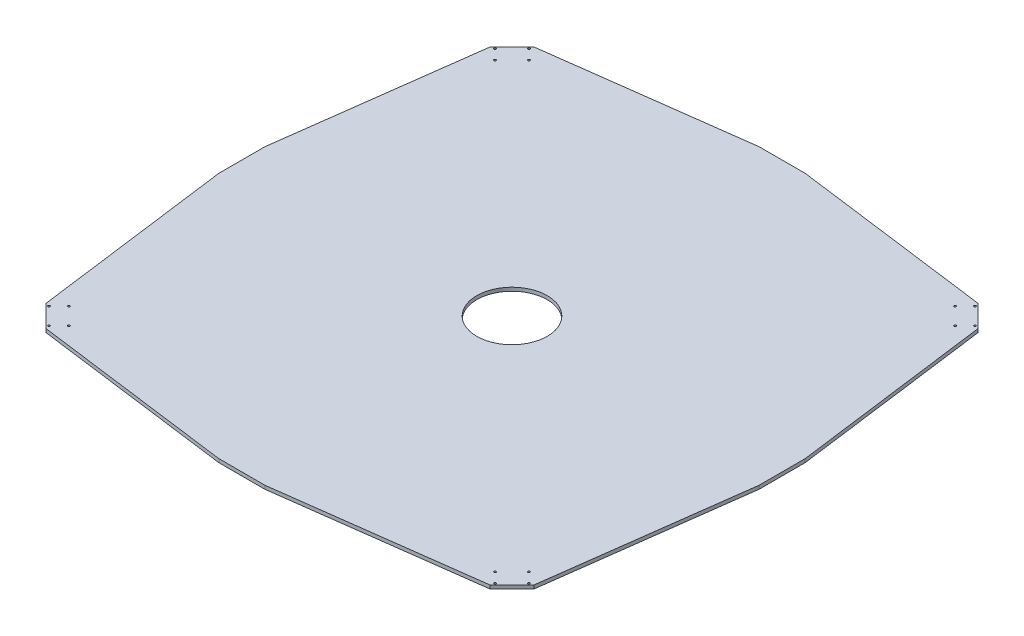
SolidWorks part; units mm, degrees
ref_plane "前视基准面" through (0, 0, 0) normal (0, 0, 1) x (1, 0, 0)
ref_plane "上视基准面" through (0, 0, 0) normal (0, 1, 0) x (1, 0, 0)
ref_plane "右视基准面" through (0, 0, 0) normal (1, 0, 0) x (0, 0, -1)
other "Configuration Table"
sketch "草图1" plane through (0, 0, 0) normal (0, 1, 0) x (1, 0, 0)
  line L0 (-314.9222, 345.9222) -> (-345.9222, 314.9222)
  line L5 (325, -325) -> (-325, 325) construction
  line L6 (325, 325) -> (-325, -325) construction
  line L7 (0, 325) -> (0, -325) construction
  line L8 (-325, 0) -> (325, 0) construction
  line L9 (314.9222, 345.9222) -> (32.7201, 383.0748)
  line L10 (314.9222, 345.9222) -> (345.9222, 314.9222)
  line L12 (-314.9222, 345.9222) -> (-32.7201, 383.0748)
  line L13 (0, 325) -> (0, 399.6983)
  line L14 (-32.7201, 383.0748) -> (32.7201, 383.0748)
  line L15 (314.9222, -345.9222) -> (32.7201, -383.0748)
  line L16 (-32.7201, -383.0748) -> (32.7201, -383.0748)
  line L17 (-314.9222, -345.9222) -> (-32.7201, -383.0748)
  line L18 (-314.9222, -345.9222) -> (-345.9222, -314.9222)
  line L19 (-345.9222, 314.9222) -> (-383.0748, 32.7201)
  line L20 (-383.0748, -32.7201) -> (-383.0748, 32.7201)
  line L21 (-345.9222, -314.9222) -> (-383.0748, -32.7201)
  line L22 (-345.9222, -314.9222) -> (-314.9222, -345.9222)
  line L23 (345.9222, -314.9222) -> (314.9222, -345.9222)
  line L24 (345.9222, -314.9222) -> (383.0748, -32.7201)
  line L25 (383.0748, 32.7201) -> (383.0748, -32.7201)
  line L26 (345.9222, 314.9222) -> (383.0748, 32.7201)
  line L27 (-337.8712, -313.8296) -> (-342.443, -318.4014)
  line L28 (-314.9222, -345.9222) -> (-293.6978, -324.6978)
  line L29 (-326.1795, -302.1379) -> (-298.6587, -329.6587)
  line L30 (-345.9222, -314.9222) -> (-325, -294)
  line L31 (-326.1795, -302.1379) -> (-329.6587, -298.6587)
  line L32 (-313.4871, -289.4455) -> (-337.8712, -313.8296)
  line L33 (-289.4455, -313.4871) -> (-313.8296, -337.8712)
  line L34 (-313.8296, -337.8712) -> (-318.4014, -342.443)
  circle A1 centre (-326.1795, -302.1379) radius 1.5
  circle A2 centre (-302.1379, -326.1795) radius 1.5
  circle A3 centre (-340.3217, -316.28) radius 1.5
  circle A4 centre (-316.28, -340.3217) radius 1.5
  circle A5 centre (0, 0) radius 50
  point P0 (0, 0)
  point P13 (0, 383.0748)
  point P24 (-330.4222, -330.4222)
  point P44 (-326.1795, -302.1379)
  point P45 (-302.1379, -326.1795)
  dimension "D6" = 3
  dimension "D7" = 20
  dimension "D8" = 100
  dimension "D1" = 650
  dimension "D2" = 650
  dimension "D3" = 31
  dimension "D4" = 142.5
  dimension "D5" = 17
extrude "凸台-拉伸2" add sketch "草图1" along normal blind 5 contours L26 L10 L9 L14 L12 L0 L19 L20 L21 L18 L17 L16 L15 L23 L24 L25 | A2 L29 A1 L32 L27 L22 L34 L33 | A1 L31 L30 L22 L27 L32 | A2 L33 L34 L18 L28 L29 region at (-172.4069, 0, -353.7562) region at (-336.0431, 0, 308.3956) region at (-322.2706, 0, 322.2706) region at (-308.3956, 0, 336.0431)
sketch "草图2" plane through (0, 5, 0) normal (0, 1, 0) x (1, 0, 0)
  line L0 (0, 0) -> (-330.4222, -330.4222) construction
pattern_circular "阵列(圆周)1" count 4 over 360 about axis through (0, 5, 0) along (0, 1, 0) of face at (-326.1795, 5, 303.6379) of face at (-340.3217, 5, 317.78) of face at (-302.1379, 5, 327.6795) of face at (-316.28, 5, 341.8217)
